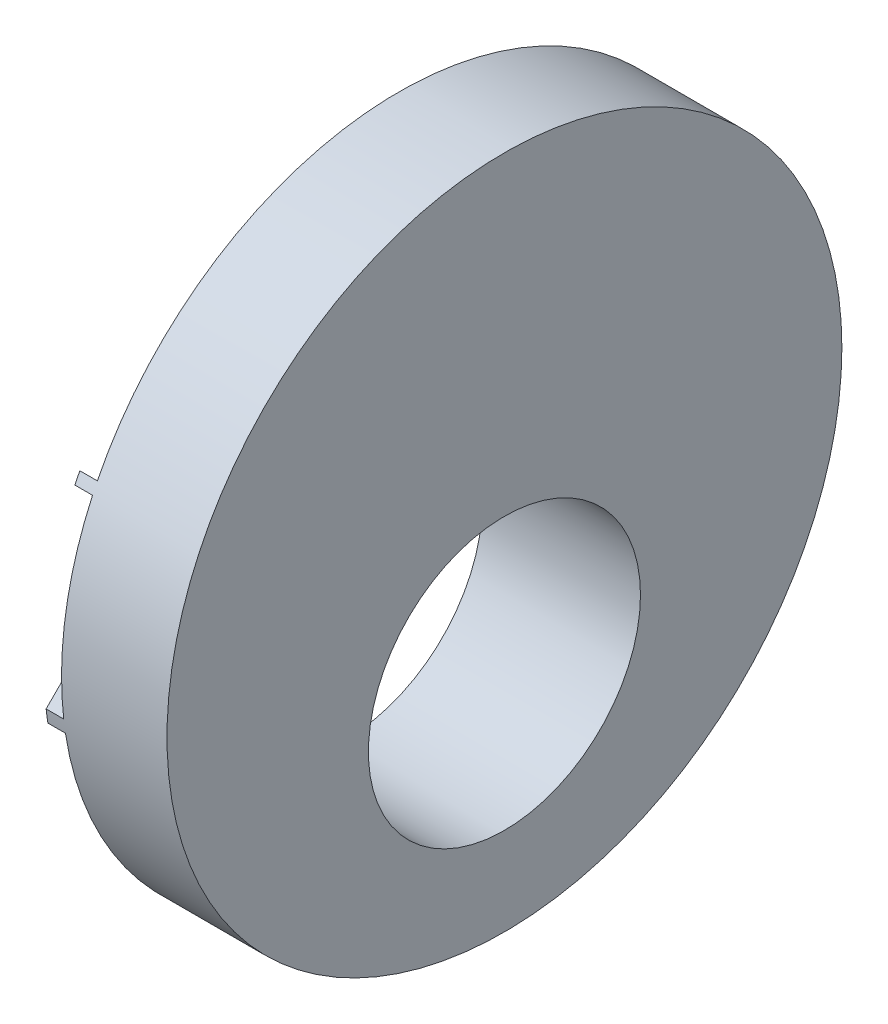
SolidWorks part; units mm, degrees
note: The reader was unsure of these and kept them because the rebuilt part matched: shared geometry of "Sketch1<3>".
ref_plane "Front Plane" through (0, 0, 0) normal (0, 0, 1) x (1, 0, 0)
ref_plane "Top Plane" through (0, 0, 0) normal (0, 1, 0) x (1, 0, 0)
ref_plane "Right Plane" through (0, 0, 0) normal (1, 0, 0) x (0, 0, -1)
sketch "Sketch1" plane through (0, 0, 0) normal (1, 0, 0) x (0, 0, -1)
  line L0 (0, 0) -> (0, -47.9999) construction
  line L1 (-20, -43.6348) -> (20, -43.6348) construction
  line L2 (0, 0) -> (0, 6.2152) construction
  line L3 (-35, 6.2152) -> (35, 6.2152)
  line L4 (35, 6.2152) -> (35, 12.5652)
  line L5 (35, 12.5652) -> (-35, 12.5652)
  line L6 (-35, 12.5652) -> (-35, 6.2152)
  circle A0 centre (0, 0) radius 48
  circle A1 centre (0, -16.1348) radius 19.35
  point P11 (0, 6.2152)
  dimension "D1" = 95.9999
  dimension "D2" = 38.7
  dimension "D4" = 27.5
  dimension "D5" = 22.35
  dimension "D3" = 40
  dimension "D6" = 70
  dimension "D7" = 6.35
extrude "Boss-Extrude1" add sketch "Sketch1" against normal blind 7.5
extrude "Boss-Extrude2" add sketch "Sketch1<3>" against normal blind 5 contours L6 L3 L4 L5
sketch "Sketch1<3>" plane through (0, 0, 0) normal (1, 0, 0) x (0, 0, -1) same geometry as "Sketch1"
sketch "Sketch2" plane through (-7.5, 0, 0) normal (-1, 0, 0) x (0, 0, 1)
  line L0 (-35, 12.5652) -> (35, 12.5652) construction
  line L1 (-35, 6.2152) -> (-35, 12.5652) construction
  line L2 (35, 12.5652) -> (35, 6.2152) construction
  line L3 (35, 6.2152) -> (-35, 6.2152) construction
  line L4 (-35, 12.5652) -> (35, 12.5652)
  line L5 (-35, 6.2152) -> (-35, 12.5652)
  line L6 (35, 12.5652) -> (35, 6.2152)
  line L7 (35, 6.2152) -> (-35, 6.2152)
  line L8 (38, 15.5652) -> (43.2512, 20.8165) construction
  line L9 (38, 3.2152) -> (47.5766, -6.3613) construction
  line L10 (-38, 15.5652) -> (-43.2512, 20.8165) construction
  line L11 (-38, 3.2152) -> (-47.5766, -6.3613) construction
  line L12 (-38, 4.2759) -> (-47.6933, -5.4174)
  line L13 (-36.9393, 15.5652) -> (-42.9017, 21.5276)
  line L14 (38, 3.2152) -> (38, 15.5652)
  line L15 (-38, 3.2152) -> (38, 3.2152)
  line L16 (-38, 15.5652) -> (-38, 3.2152)
  line L17 (38, 15.5652) -> (-38, 15.5652)
  line L18 (38, 3.2152) -> (38, 4.2759) construction
  line L19 (-38, 3.2152) -> (-36.9393, 3.2152) construction
  line L20 (-38, 15.5652) -> (-38, 14.5045) construction
  line L21 (38, 15.5652) -> (36.9393, 15.5652) construction
  line L22 (36.9393, 3.2152) -> (47.4433, -7.2888)
  line L23 (38, 14.5045) -> (43.5909, 20.0955)
  line L24 (-36.9393, 3.2152) -> (-47.4433, -7.2888)
  line L25 (-38, 14.5045) -> (-43.5909, 20.0955)
  line L26 (38, 4.2759) -> (47.6933, -5.4174)
  line L27 (36.9393, 15.5652) -> (42.9017, 21.5276)
  line L28 (38.5303, 3.7455) -> (48.1069, -5.831) construction
  line L29 (37.4697, 2.6849) -> (47.0462, -6.8917) construction
  line L30 (38.5303, 15.0349) -> (43.7816, 20.2861) construction
  line L31 (37.4697, 16.0955) -> (42.7209, 21.3468) construction
  line L32 (-38.5303, 15.0349) -> (-43.7816, 20.2861) construction
  line L33 (-37.4697, 16.0955) -> (-42.7209, 21.3468) construction
  line L34 (-38.5303, 3.7455) -> (-48.1069, -5.831) construction
  line L35 (-37.4697, 2.6849) -> (-47.0462, -6.8917) construction
  line L36 (38, 4.2759) -> (38, 14.5045)
  line L37 (36.9393, 3.2152) -> (38, 3.2152) construction
  line L38 (36.9393, 15.5652) -> (-36.9393, 15.5652)
  line L39 (-38, 14.5045) -> (-38, 3.7107)
  line L40 (-36.9393, 15.5652) -> (-38, 15.5652) construction
  line L41 (38, 14.5045) -> (38, 15.5652) construction
  line L42 (-38, 3.7107) -> (-38, 3.2152) construction
  line L43 (-36.9393, 3.2152) -> (36.9393, 3.2152)
  circle A0 centre (0, 0) radius 48 construction
  arc A1 (47.4433, -7.2888) -> (47.6933, -5.4174) centre (0, 0) ccw
  arc A2 (-42.9017, 21.5276) -> (-43.5909, 20.0955) centre (0, 0) ccw
  arc A3 (-47.6933, -5.4174) -> (-47.4433, -7.2888) centre (0, 0) ccw
  arc A4 (43.5909, 20.0955) -> (42.9017, 21.5276) centre (0, 0) ccw
  line M5 (-35, 12.5652) -> (35, 12.5652)
  line M6 (35, 12.5652) -> (35, 6.2152)
  line M7 (35, 6.2152) -> (-35, 6.2152)
  line M8 (-35, 6.2152) -> (-35, 12.5652)
  dimension "D2" = 135
  dimension "D3" = 135
  dimension "D4" = 135
  dimension "D5" = 135
  dimension "D1" = 3
  dimension "D6" = 0.75
  dimension "D7" = 0.75
extrude "Boss-Extrude3" add sketch "Sketch2" along normal blind 10 contours L18 L21 L20 L19 M8 M5 M6 M7
sketch "Sketch3" plane through (-7.5, 0, 0) normal (-1, 0, 0) x (0, 0, 1)
  line L0 (35, 6.2152) -> (-35, 6.2152) construction
  line L1 (14.8795, 6.2152) -> (-14.8795, 6.2152)
  circle A0 centre (0, -16.1348) radius 19.35 construction
  circle A1 centre (0, -16.1348) radius 19.35
  arc A5 (26.85, -16.1348) -> (26.85, -16.1348) centre (0, -16.1348) ccw
  arc A6 (-14.8795, 6.2152) -> (14.8795, 6.2152) centre (0, -16.1348) ccw
  dimension "D1" = 7.5
extrude "Boss-Extrude4" add sketch "Sketch3" along normal blind 15
sketch "Sketch4" plane through (-7.5, 0, 0) normal (-1, 0, 0) x (0, 0, 1)
  circle A2 centre (0, 0) radius 40.5
  circle A6 centre (0, 0) radius 48 construction
  circle A7 centre (0, 0) radius 48
  dimension "D1" = 7.5
extrude "Boss-Extrude5" add sketch "Sketch4" along normal blind 7.5
